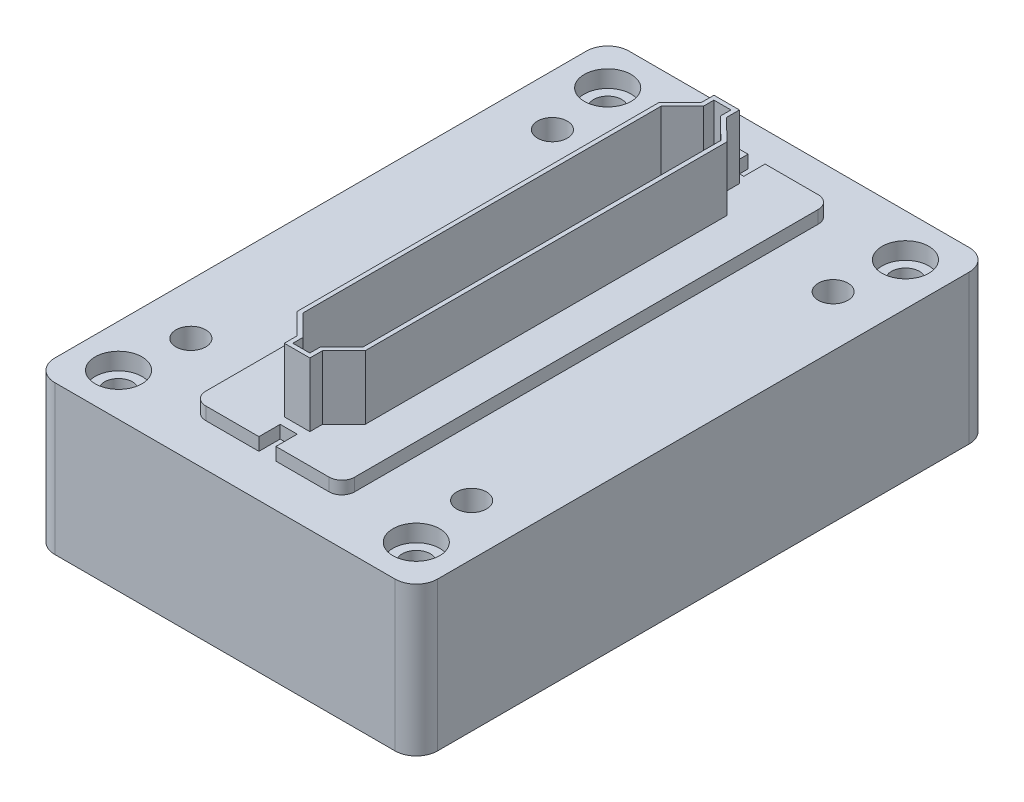
SolidWorks part; units mm, degrees
ref_plane "Front Plane" through (0, 0, 0) normal (0, 0, 1) x (1, 0, 0)
ref_plane "Top Plane" through (0, 0, 0) normal (0, 1, 0) x (1, 0, 0)
ref_plane "Right Plane" through (0, 0, 0) normal (1, 0, 0) x (0, 0, -1)
sketch "Sketch2" plane through (0, 0, 0) normal (0, 1, 0) x (1, 0, 0)
  line L1 (45, 67.5) -> (-45, 67.5)
  line L2 (45, 67.5) -> (45, -67.5)
  line L3 (45, -67.5) -> (-45, -67.5)
  line L4 (-45, 67.5) -> (-45, -67.5)
  line L5 (45, 67.5) -> (-45, -67.5) construction
  line L6 (45, -67.5) -> (-45, 67.5) construction
  point P0 (0, 0)
  dimension "D1" = 90
  dimension "D2" = 135
extrude "Boss-Extrude1" add sketch "Sketch2" along normal blind 35
fillet "Fillet1" radius 5 4 edges at (45, 17.5, -67.5) (45, 17.5, 67.5) (-45, 17.5, 67.5) (-45, 17.5, -67.5)
hole_wizard "CBORE for M6 Hex Head Bolt1" positions "3DSketch1" profile "Sketch6" counterbore size "M6" standard "DIN"
sketch3d "3DSketch1"
  line L1 (40, 35, -67.5) -> (-40, 35, -67.5) construction
  line L2 (-45, 35, -62.5) -> (-45, 35, 62.5) construction
  point P0 (-35, 35, -57.5)
  point P11 (-35.5242, 35, -57.2047)
  point P12 (-35.5242, 35, -57.2047)
  dimension "D1" = 10
  dimension "D2" = 10
sketch "Sketch6" plane through (-35, 35, -57.5) normal (1, 0, 0) x (0, 0, 1)
  line L0 (0, 0) -> (0, 43.9828)
  line L1 (0, 43.9828) -> (3.3, 42)
  line L2 (3.3, 42) -> (3.3, 4)
  line L3 (3.3, 4) -> (5.5, 4)
  line L4 (5.5, 4) -> (5.5, 0)
  line L5 (5.5, 0) -> (0, 0)
  line L10 (0, 43.9828) -> (-3.3, 42) construction
  line L11 (0, -6.35) -> (0, 107.95) construction
  dimension "Hole Dia." = 6.6
  dimension "Hole Depth" = 42
  dimension "C'Bore Dia." = 11
  dimension "C'Bore Depth" = 4
  dimension "Drill Angle" = 118
ref_axis "Axis1" through (0, -1.5, 0) along (0, 1, 0)
sketch "Sketch8" plane through (0, 35, 0) normal (0, 1, 0) x (1, 0, 0)
  line L0 (40, 67.5) -> (-40, 67.5) construction
  line L1 (-45, 62.5) -> (-45, -62.5) construction
  circle A0 centre (-33, 42.5) radius 3.5
  dimension "D1" = 7
  dimension "D2" = 25
  dimension "D3" = 12
extrude "Cut-Extrude1" cut sketch "Sketch8" against normal blind 10
mirror "Mirror1" about plane through (0, 0, 0) normal (1, 0, 0) of "Cut-Extrude1", "CBORE for M6 Hex Head Bolt1"
mirror "Mirror2" about plane through (0, 0, 0) normal (0, 0, 1) of "Mirror1"
sketch "Sketch9" plane through (0, 35, 0) normal (0, 1, 0) x (1, 0, 0)
  line L0 (0, 0) -> (17.5, 0) construction
  line L1 (14.5, -57.5) -> (2, -57.5)
  line L2 (17.5, -54.5) -> (17.5, 54.5)
  line L3 (14.5, 57.5) -> (2, 57.5)
  line L4 (-17.5, -54.5) -> (-17.5, 54.5)
  line L5 (17.5, -57.5) -> (-17.5, 57.5) construction
  line L6 (17.5, 57.5) -> (-17.5, -57.5) construction
  line L8 (-2, 57.5) -> (-2, 52.5)
  line L9 (-2, 52.5) -> (2, 52.5)
  line L10 (2, 57.5) -> (2, 52.5)
  line L11 (-2, 57.5) -> (2, 52.5) construction
  line L12 (-2, 52.5) -> (2, 57.5) construction
  line L13 (-2, -57.5) -> (-2, -52.5)
  line L14 (-2, -52.5) -> (2, -52.5)
  line L15 (2, -57.5) -> (2, -52.5)
  line L16 (-2, 57.5) -> (-14.5, 57.5)
  line L17 (-2, -57.5) -> (-14.5, -57.5)
  arc A0 (-14.5, 57.5) -> (-17.5, 54.5) centre (-14.5, 54.5) ccw
  arc A1 (17.5, 54.5) -> (14.5, 57.5) centre (14.5, 54.5) ccw
  arc A2 (14.5, -57.5) -> (17.5, -54.5) centre (14.5, -54.5) ccw
  arc A3 (-14.5, -57.5) -> (-17.5, -54.5) centre (-14.5, -54.5) cw
  point P0 (0, 0)
  point P18 (0, 55)
  dimension "D3" = 3
  dimension "D1" = 115
  dimension "D2" = 35
  dimension "D4" = 4
  dimension "D5" = 5
extrude "Boss-Extrude2" add sketch "Sketch9" along normal blind 3 separate body
sketch "Sketch10" plane through (0, 38, 0) normal (0, 1, 0) x (1, 0, 0)
  line L0 (2.9753, 47.5) -> (8, 42.5)
  line L2 (8, -42.5) -> (8, 42.5)
  line L4 (-8, -42.5) -> (-8, 42.5)
  line L5 (8, -42.5) -> (-8, 42.5) construction
  line L6 (8, 42.5) -> (-8, -42.5) construction
  line L7 (-3.0247, 50.5) -> (2.9753, 50.5)
  line L8 (-3.0247, 50.5) -> (-3.0247, 47.5)
  line L10 (2.9753, 50.5) -> (2.9753, 47.5)
  line L11 (-3.0247, 50.5) -> (2.9753, 44.2507) construction
  line L12 (-3.0247, 44.2507) -> (2.9753, 50.5) construction
  line L13 (-3.0247, 47.5) -> (-8, 42.5)
  line L14 (0, 0) -> (8, 0) construction
  line L15 (-3.0247, -47.5) -> (-8, -42.5)
  line L16 (-3.0247, -50.5) -> (-3.0247, -47.5)
  line L17 (2.9753, -47.5) -> (8, -42.5)
  line L18 (2.9753, -50.5) -> (2.9753, -47.5)
  line L19 (-3.0247, -50.5) -> (2.9753, -50.5)
  line L20 (7, -42.0843) -> (7, 42.0843)
  line L21 (1.9753, 47.0843) -> (7, 42.0843)
  line L22 (1.9753, 49.5) -> (1.9753, 47.0843)
  line L23 (-2.0247, 49.5) -> (1.9753, 49.5)
  line L24 (-2.0247, 49.5) -> (-2.0247, 47.0872)
  line L25 (-2.0247, 47.0872) -> (-7, 42.0872)
  line L26 (-7, -42.0872) -> (-7, 42.0872)
  line L27 (-2.0247, -47.0872) -> (-7, -42.0872)
  line L28 (-2.0247, -49.5) -> (-2.0247, -47.0872)
  line L29 (-2.0247, -49.5) -> (1.9753, -49.5)
  line L30 (1.9753, -49.5) -> (1.9753, -47.0843)
  line L31 (1.9753, -47.0843) -> (7, -42.0843)
  point P0 (0, 0)
  point P6 (-0.0247, 47.3753)
  point P15 (0, 0)
  point P16 (0, 0)
  dimension "D1" = 6
  dimension "D2" = 85
  dimension "D3" = 16
  dimension "D4" = 1
  dimension "D5" = 3
extrude "Boss-Extrude3" add sketch "Sketch10" along normal blind 15
